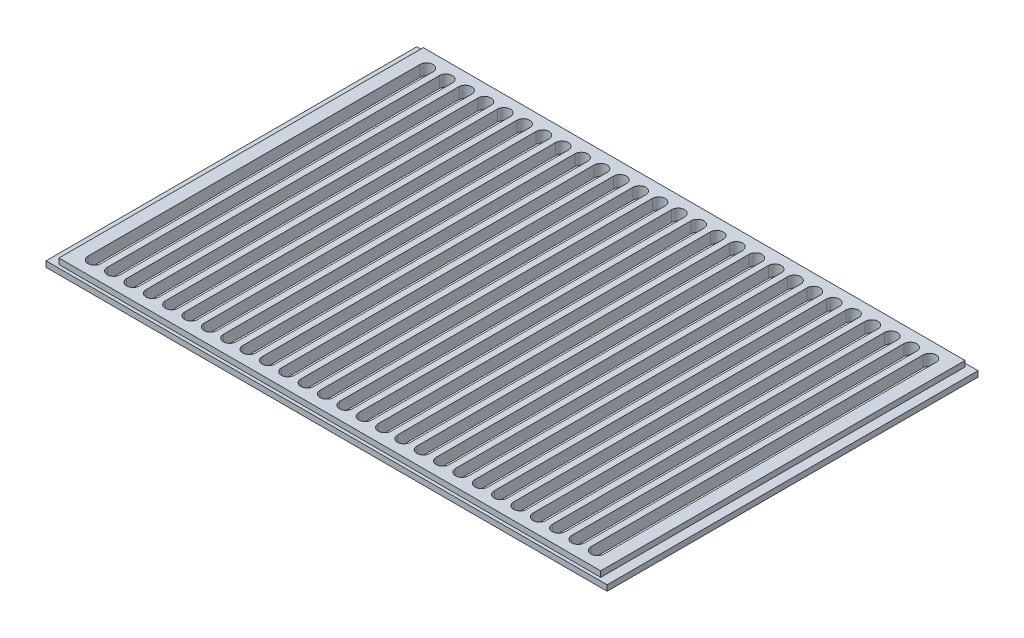
SolidWorks part; units mm, degrees
ref_plane "Front Plane" through (0, 0, 0) normal (0, 0, 1) x (1, 0, 0)
ref_plane "Top Plane" through (0, 0, 0) normal (0, 1, 0) x (1, 0, 0)
ref_plane "Right Plane" through (0, 0, 0) normal (1, 0, 0) x (0, 0, -1)
sketch "Sketch1" plane through (0, 0, 0) normal (0, 1, 0) x (1, 0, 0)
  line L1 (0, 0) -> (174, 0)
  line L2 (0, 0) -> (0, 115)
  line L3 (0, 115) -> (174, 115)
  line L4 (174, 0) -> (174, 115)
  dimension "D1" = 115
  dimension "D2" = 174
extrude "Boss-Extrude1" add sketch "Sketch1" along normal blind 1.75
sketch "Sketch2" plane through (0, 1.75, 0) normal (0, 1, 0) x (1, 0, 0)
  line L0 (0, 115) -> (0, 0) construction
  line L1 (3, 114) -> (171, 114)
  line L2 (3, 114) -> (3, 1)
  line L3 (3, 1) -> (171, 1)
  line L4 (171, 114) -> (171, 1)
  line L5 (174, 0) -> (174, 115) construction
  line L6 (0, 0) -> (174, 0) construction
  line L7 (174, 115) -> (0, 115) construction
  line L8 (4, 113) -> (170, 113)
  line L9 (170, 113) -> (170, 2)
  line L10 (4, 2) -> (170, 2)
  line L11 (4, 113) -> (4, 2)
  dimension "D1" = 3
  dimension "D2" = 3
  dimension "D3" = 1
  dimension "D4" = 1
  dimension "D5" = 1
extrude "Boss-Extrude2" add sketch "Sketch2" along normal blind 1.75
sketch "Sketch3" plane through (0, 1.75, 0) normal (0, 1, 0) x (1, 0, 0)
  line L0 (0, 109) -> (174, 109) construction
  line L1 (0, 115) -> (0, 0) construction
  line L2 (174, 0) -> (174, 115) construction
  line L3 (0, 6) -> (174, 6) construction
  line L4 (170, 113) -> (4, 113) construction
  line L5 (4, 2) -> (170, 2) construction
  line L6 (9, 109) -> (9, 6) construction
  line L7 (11, 109) -> (11, 6)
  line L8 (7, 109) -> (7, 6)
  line L9 (4, 113) -> (4, 2) construction
  line L10 (15, 109) -> (15, 6) construction
  line L13 (17, 109) -> (17, 6)
  line L16 (13, 109) -> (13, 6)
  line L19 (21, 109) -> (21, 6) construction
  line L22 (23, 109) -> (23, 6)
  line L25 (19, 109) -> (19, 6)
  line L28 (27, 109) -> (27, 6) construction
  line L31 (29, 109) -> (29, 6)
  line L34 (25, 109) -> (25, 6)
  line L37 (33, 109) -> (33, 6) construction
  line L40 (35, 109) -> (35, 6)
  line L43 (31, 109) -> (31, 6)
  line L46 (39, 109) -> (39, 6) construction
  line L49 (41, 109) -> (41, 6)
  line L52 (37, 109) -> (37, 6)
  line L55 (45, 109) -> (45, 6) construction
  line L58 (47, 109) -> (47, 6)
  line L61 (43, 109) -> (43, 6)
  line L64 (51, 109) -> (51, 6) construction
  line L67 (53, 109) -> (53, 6)
  line L70 (49, 109) -> (49, 6)
  line L73 (57, 109) -> (57, 6) construction
  line L76 (59, 109) -> (59, 6)
  line L79 (55, 109) -> (55, 6)
  line L82 (63, 109) -> (63, 6) construction
  line L85 (65, 109) -> (65, 6)
  line L88 (61, 109) -> (61, 6)
  line L91 (69, 109) -> (69, 6) construction
  line L94 (71, 109) -> (71, 6)
  line L97 (67, 109) -> (67, 6)
  line L100 (75, 109) -> (75, 6) construction
  line L103 (77, 109) -> (77, 6)
  line L106 (73, 109) -> (73, 6)
  line L109 (81, 109) -> (81, 6) construction
  line L112 (83, 109) -> (83, 6)
  line L115 (79, 109) -> (79, 6)
  line L118 (87, 109) -> (87, 6) construction
  line L121 (89, 109) -> (89, 6)
  line L124 (85, 109) -> (85, 6)
  line L127 (93, 109) -> (93, 6) construction
  line L130 (95, 109) -> (95, 6)
  line L133 (91, 109) -> (91, 6)
  line L136 (99, 109) -> (99, 6) construction
  line L139 (101, 109) -> (101, 6)
  line L142 (97, 109) -> (97, 6)
  line L145 (105, 109) -> (105, 6) construction
  line L148 (107, 109) -> (107, 6)
  line L151 (103, 109) -> (103, 6)
  line L154 (111, 109) -> (111, 6) construction
  line L157 (113, 109) -> (113, 6)
  line L160 (109, 109) -> (109, 6)
  line L163 (117, 109) -> (117, 6) construction
  line L166 (119, 109) -> (119, 6)
  line L169 (115, 109) -> (115, 6)
  line L172 (123, 109) -> (123, 6) construction
  line L173 (125, 109) -> (125, 6)
  line L174 (121, 109) -> (121, 6)
  line L175 (129, 109) -> (129, 6) construction
  line L176 (131, 109) -> (131, 6)
  line L177 (127, 109) -> (127, 6)
  line L178 (135, 109) -> (135, 6) construction
  line L179 (137, 109) -> (137, 6)
  line L180 (133, 109) -> (133, 6)
  line L181 (141, 109) -> (141, 6) construction
  line L182 (143, 109) -> (143, 6)
  line L183 (139, 109) -> (139, 6)
  line L184 (147, 109) -> (147, 6) construction
  line L185 (149, 109) -> (149, 6)
  line L186 (145, 109) -> (145, 6)
  line L187 (153, 109) -> (153, 6) construction
  line L188 (155, 109) -> (155, 6)
  line L189 (151, 109) -> (151, 6)
  line L190 (159, 109) -> (159, 6) construction
  line L191 (161, 109) -> (161, 6)
  line L192 (157, 109) -> (157, 6)
  line L193 (165, 109) -> (165, 6) construction
  line L194 (167, 109) -> (167, 6)
  line L195 (163, 109) -> (163, 6)
  arc A0 (11, 109) -> (7, 109) centre (9, 109) ccw
  arc A1 (7, 6) -> (11, 6) centre (9, 6) ccw
  arc A110 (17, 109) -> (13, 109) centre (15, 109) ccw
  arc A111 (13, 6) -> (17, 6) centre (15, 6) ccw
  arc A112 (23, 109) -> (19, 109) centre (21, 109) ccw
  arc A113 (19, 6) -> (23, 6) centre (21, 6) ccw
  arc A114 (29, 109) -> (25, 109) centre (27, 109) ccw
  arc A115 (25, 6) -> (29, 6) centre (27, 6) ccw
  arc A116 (35, 109) -> (31, 109) centre (33, 109) ccw
  arc A117 (31, 6) -> (35, 6) centre (33, 6) ccw
  arc A118 (41, 109) -> (37, 109) centre (39, 109) ccw
  arc A119 (37, 6) -> (41, 6) centre (39, 6) ccw
  arc A120 (47, 109) -> (43, 109) centre (45, 109) ccw
  arc A121 (43, 6) -> (47, 6) centre (45, 6) ccw
  arc A122 (53, 109) -> (49, 109) centre (51, 109) ccw
  arc A123 (49, 6) -> (53, 6) centre (51, 6) ccw
  arc A124 (59, 109) -> (55, 109) centre (57, 109) ccw
  arc A125 (55, 6) -> (59, 6) centre (57, 6) ccw
  arc A126 (65, 109) -> (61, 109) centre (63, 109) ccw
  arc A127 (61, 6) -> (65, 6) centre (63, 6) ccw
  arc A128 (71, 109) -> (67, 109) centre (69, 109) ccw
  arc A129 (67, 6) -> (71, 6) centre (69, 6) ccw
  arc A130 (77, 109) -> (73, 109) centre (75, 109) ccw
  arc A131 (73, 6) -> (77, 6) centre (75, 6) ccw
  arc A132 (83, 109) -> (79, 109) centre (81, 109) ccw
  arc A133 (79, 6) -> (83, 6) centre (81, 6) ccw
  arc A134 (89, 109) -> (85, 109) centre (87, 109) ccw
  arc A135 (85, 6) -> (89, 6) centre (87, 6) ccw
  arc A136 (95, 109) -> (91, 109) centre (93, 109) ccw
  arc A137 (91, 6) -> (95, 6) centre (93, 6) ccw
  arc A138 (101, 109) -> (97, 109) centre (99, 109) ccw
  arc A139 (97, 6) -> (101, 6) centre (99, 6) ccw
  arc A140 (107, 109) -> (103, 109) centre (105, 109) ccw
  arc A141 (103, 6) -> (107, 6) centre (105, 6) ccw
  arc A142 (113, 109) -> (109, 109) centre (111, 109) ccw
  arc A143 (109, 6) -> (113, 6) centre (111, 6) ccw
  arc A144 (119, 109) -> (115, 109) centre (117, 109) ccw
  arc A145 (115, 6) -> (119, 6) centre (117, 6) ccw
  arc A146 (125, 109) -> (121, 109) centre (123, 109) ccw
  arc A147 (121, 6) -> (125, 6) centre (123, 6) ccw
  arc A148 (131, 109) -> (127, 109) centre (129, 109) ccw
  arc A149 (127, 6) -> (131, 6) centre (129, 6) ccw
  arc A150 (137, 109) -> (133, 109) centre (135, 109) ccw
  arc A151 (133, 6) -> (137, 6) centre (135, 6) ccw
  arc A152 (143, 109) -> (139, 109) centre (141, 109) ccw
  arc A153 (139, 6) -> (143, 6) centre (141, 6) ccw
  arc A154 (149, 109) -> (145, 109) centre (147, 109) ccw
  arc A155 (145, 6) -> (149, 6) centre (147, 6) ccw
  arc A156 (155, 109) -> (151, 109) centre (153, 109) ccw
  arc A157 (151, 6) -> (155, 6) centre (153, 6) ccw
  arc A158 (161, 109) -> (157, 109) centre (159, 109) ccw
  arc A159 (157, 6) -> (161, 6) centre (159, 6) ccw
  arc A160 (167, 109) -> (163, 109) centre (165, 109) ccw
  arc A161 (163, 6) -> (167, 6) centre (165, 6) ccw
  point P14 (9, 57.5)
  point P25 (15, 57.5)
  point P32 (21, 57.5)
  point P39 (27, 57.5)
  point P46 (33, 57.5)
  point P53 (39, 57.5)
  point P60 (45, 57.5)
  point P67 (51, 57.5)
  point P74 (57, 57.5)
  point P81 (63, 57.5)
  point P88 (69, 57.5)
  point P95 (75, 57.5)
  point P102 (81, 57.5)
  point P109 (87, 57.5)
  point P116 (93, 57.5)
  point P123 (99, 57.5)
  point P130 (105, 57.5)
  point P137 (111, 57.5)
  point P144 (117, 57.5)
  point P151 (123, 57.5)
  point P158 (129, 57.5)
  point P165 (135, 57.5)
  point P172 (141, 57.5)
  point P179 (147, 57.5)
  point P186 (153, 57.5)
  point P193 (159, 57.5)
  point P200 (165, 57.5)
  dimension "D1" = 4
  dimension "D2" = 4
  dimension "D3" = 4
  dimension "D4" = 3
  dimension "D5" = 27
extrude "Cut-Extrude1" cut sketch "Sketch3" against normal up to surface (1.75 mm away) up to face at (87, 0, -57.5)
sketch "Sketch4" plane through (0, 3.5, 0) normal (0, 1, 0) x (1, 0, 0)
  line L1 (4, 113) -> (170, 113)
  line L2 (4, 113) -> (4, 2)
  line L3 (4, 2) -> (170, 2)
  line L4 (170, 113) -> (170, 2)
extrude "Boss-Extrude3" add sketch "Sketch4" against normal up to surface (1.75 mm away) up to face at (87, 1.75, -57.5)
extrude "Cut-Extrude2" cut sketch "Sketch3<2>" against normal through all both and the other way through all
sketch "Sketch3<2>" plane through (0, 1.75, 0) normal (0, 1, 0) x (1, 0, 0) same geometry as "Sketch3"
